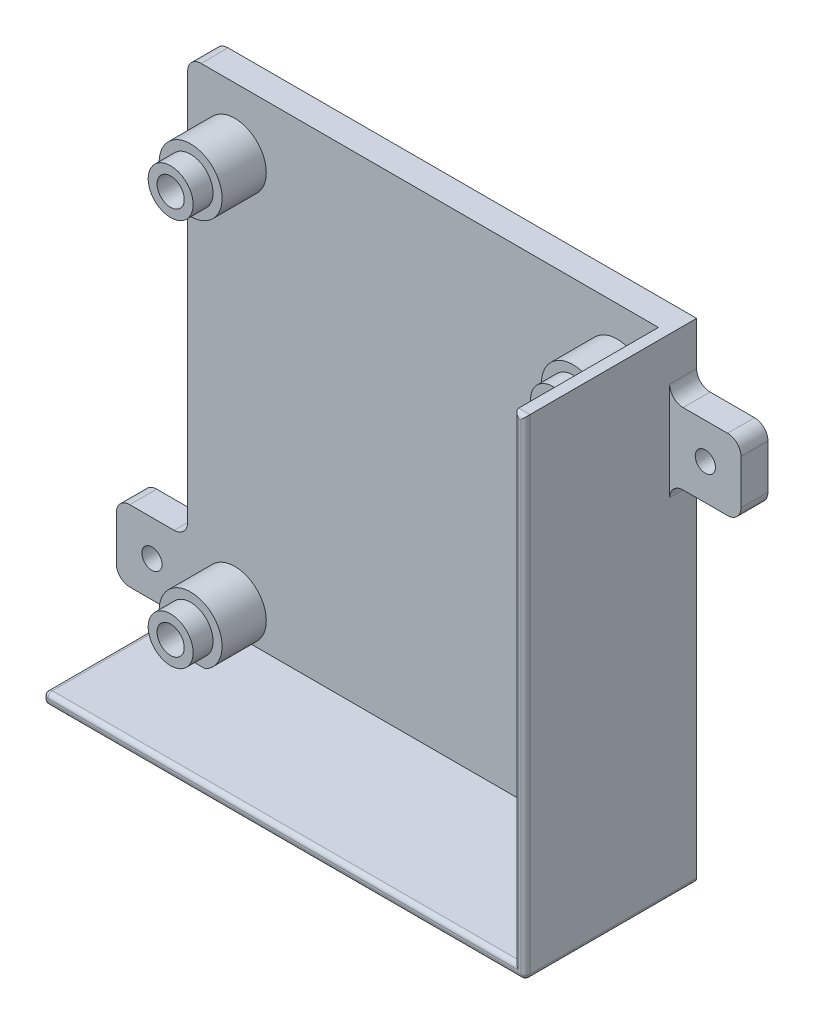
SolidWorks part; units mm, degrees
material "ABS"
ref_plane "X-Y Datum" through (0, 0, 0) normal (0, 0, 1) x (1, 0, 0)
ref_plane "X-Z Datum" through (0, 0, 0) normal (0, 1, 0) x (1, 0, 0)
ref_plane "Y-Z Datum" through (0, 0, 0) normal (1, 0, 0) x (0, 0, -1)
sketch "Sketch1" plane through (0, 0, 0) normal (0, 0, 1) x (1, 0, 0)
  line L1 (-52.3875, 53.1812) -> (52.3875, 53.1812)
  line L2 (-52.3875, 53.1812) -> (-52.3875, -53.1812)
  line L3 (-52.3875, -53.1812) -> (52.3875, -53.1812)
  line L4 (52.3875, 53.1812) -> (52.3875, -53.1812)
  line L5 (-52.3875, 53.1812) -> (52.3875, -53.1812) construction
  line L6 (-52.3875, -53.1812) -> (52.3875, 53.1812) construction
  point P0 (0, 0)
  dimension "D1" = 104.775
  dimension "D2" = 106.3625
extrude "Boss-Extrude1" add sketch "Sketch1" along normal blind 6
sketch "Sketch2" plane through (0, 0, 0) normal (0, 0, 1) x (1, 0, 0)
  line L3 (-52.3875, -53.1812) -> (-52.3875, -55.6812)
  line L4 (54.8875, 53.1812) -> (52.3875, 53.1812)
  line L5 (54.8875, -55.6812) -> (54.8875, 53.1812)
  line L6 (-52.3875, -55.6812) -> (54.8875, -55.6812)
  line L7 (54.8875, -55.6812) -> (54.8875, 53.1812)
  line L8 (-52.3875, -55.6812) -> (54.8875, -55.6812)
  line L9 (52.3875, -53.1812) -> (52.3875, 53.1812) construction
  line L10 (-52.3875, -53.1812) -> (52.3875, -53.1812) construction
  line L11 (52.3875, -53.1812) -> (52.3875, 53.1812)
  line L12 (-52.3875, -53.1812) -> (52.3875, -53.1812)
  dimension "D1" = 2.5
extrude "Boss-Extrude2" add sketch "Sketch2" along normal blind 38.1
sketch "Sketch3" plane through (0, 0, 6) normal (0, 0, 1) x (1, 0, 0)
  circle A0 centre (-41.882, 39.351) radius 3.025
  circle A1 centre (43.208, 39.351) radius 3.025
  circle A2 centre (43.208, -47.009) radius 3.025
  circle A3 centre (-41.882, -47.009) radius 3.025
  circle A4 centre (43.208, 39.351) radius 5
  circle A5 centre (-41.882, 39.351) radius 5
  circle A6 centre (-41.882, -47.009) radius 5
  circle A7 centre (43.208, -47.009) radius 5
  point P0 (-41.882, 39.351)
  point P1 (-41.882, -47.009)
  point P3 (43.208, -47.009)
  point P5 (43.208, 39.351)
  dimension "D1" = 6.05
  dimension "D2" = 10
extrude "Boss-Extrude3" add sketch "Sketch3" along normal blind 14.2875
sketch "Sketch4" plane through (0, 0, 6) normal (0, 0, 1) x (1, 0, 0)
  circle A0 centre (43.208, 39.351) radius 7
  circle A1 centre (-41.882, 39.351) radius 7
  circle A2 centre (-41.882, -47.009) radius 7
  circle A3 centre (43.208, -47.009) radius 7
  circle A5 centre (-41.882, -47.009) radius 3.025
  circle A6 centre (-41.882, -47.009) radius 3.025
  circle A7 centre (43.208, -47.009) radius 3.025
  circle A8 centre (43.208, -47.009) radius 3.025
  circle A9 centre (43.208, 39.351) radius 3.025
  circle A10 centre (43.208, 39.351) radius 3.025
  circle A11 centre (-41.882, 39.351) radius 3.025
  circle A12 centre (-41.882, 39.351) radius 3.025
  dimension "D1" = 14
  dimension "D2" = 0
  dimension "D3" = 0
  dimension "D4" = 0
  dimension "D5" = 0
extrude "Boss-Extrude4" add sketch "Sketch4" along normal blind 9.8425
sketch "Sketch6" plane through (0, 0, 0) normal (0, 0, 1) x (1, 0, 0)
  line L0 (-68.2625, -39.8062) -> (-52.3875, -55.6812)
  line L1 (-52.3875, -55.6812) -> (-68.2625, -55.6812)
  line L2 (-52.3875, -55.6812) -> (-52.3875, -39.8062)
  line L3 (-52.3875, -39.8062) -> (-68.2625, -39.8062)
  line L4 (-68.2625, -55.6812) -> (-68.2625, -39.8062)
  line L5 (54.8875, -55.6812) -> (54.8875, 53.1812) construction
  line L6 (54.8875, 40.4812) -> (70.7625, 40.4812)
  line L7 (54.8875, 40.4812) -> (54.8875, 24.6062)
  line L8 (54.8875, 24.6062) -> (70.7625, 24.6062)
  line L9 (70.7625, 40.4812) -> (70.7625, 24.6062)
  line L10 (54.8875, 24.6062) -> (70.7625, 40.4812)
  line L11 (54.8875, 53.1812) -> (52.3875, 53.1812) construction
  circle A0 centre (-60.325, -47.7437) radius 2 construction
  circle A1 centre (62.825, 32.5437) radius 2 construction
  dimension "D1" = 4
  dimension "D6" = 4
  dimension "D2" = 15.875
  dimension "D3" = 15.875
  dimension "D4" = 15.875
  dimension "D5" = 15.875
  dimension "D7" = 12.7
extrude "Boss-Extrude5" add sketch "Sketch6" along normal blind 6 contours L2 L3 L0 | L4 L1 L0 | L10 L8 L9 | L7 L10 L6 region at (-57.6792, -45.0979, 0) region at (-62.9708, -50.3896, 0) region at (60.1792, 35.1896, 0) region at (65.4708, 29.8979, 0)
hole_wizard "M4 Clearance Hole1" positions "Sketch7" profile "Sketch8" hole size "M4" standard "ANSI Metric" end condition through all
sketch "Sketch7" plane through (0, 0, 6) normal (0, 0, 1) x (1, 0, 0)
  point P0 (62.825, 32.5437)
  point P3 (-60.325, -47.7437)
sketch "Sketch8" plane through (62.825, 32.5437, 6) normal (1, 0, 0) x (0, -1, 0)
  line L0 (0, 0) -> (0, 6)
  line L1 (0, 6) -> (2.25, 6)
  line L2 (2.25, 6) -> (2.25, 0)
  line L5 (2.25, 0) -> (0, 0)
  line L11 (0, -6.35) -> (0, 107.95) construction
  dimension "Thru Hole Dia." = 4.5
  dimension "Thru Hole Depth" = 6
fillet "Fillet2" radius 3 8 edges at (70.7625, 24.6062, 3) (70.7625, 40.4812, 3) (54.8875, 40.4812, 3) (54.8875, 24.6062, 3) (-68.2625, -55.6812, 3) (-68.2625, -39.8062, 3) (-52.3875, -39.8062, 3) (-52.3875, 53.1812, 3)
fillet "Fillet3" radius 1 9 edges at (52.3875, 0, 38.1) (53.6375, 53.1812, 38.1) (54.8875, -1.25, 38.1) (-52.3875, -54.4312, 38.1) (0, -53.1812, 38.1) (54.8875, -55.6812, 19.05) (1.25, -55.6812, 38.1) (-52.3875, -53.1812, 22.05) (-52.3875, -55.6812, 22.05)
